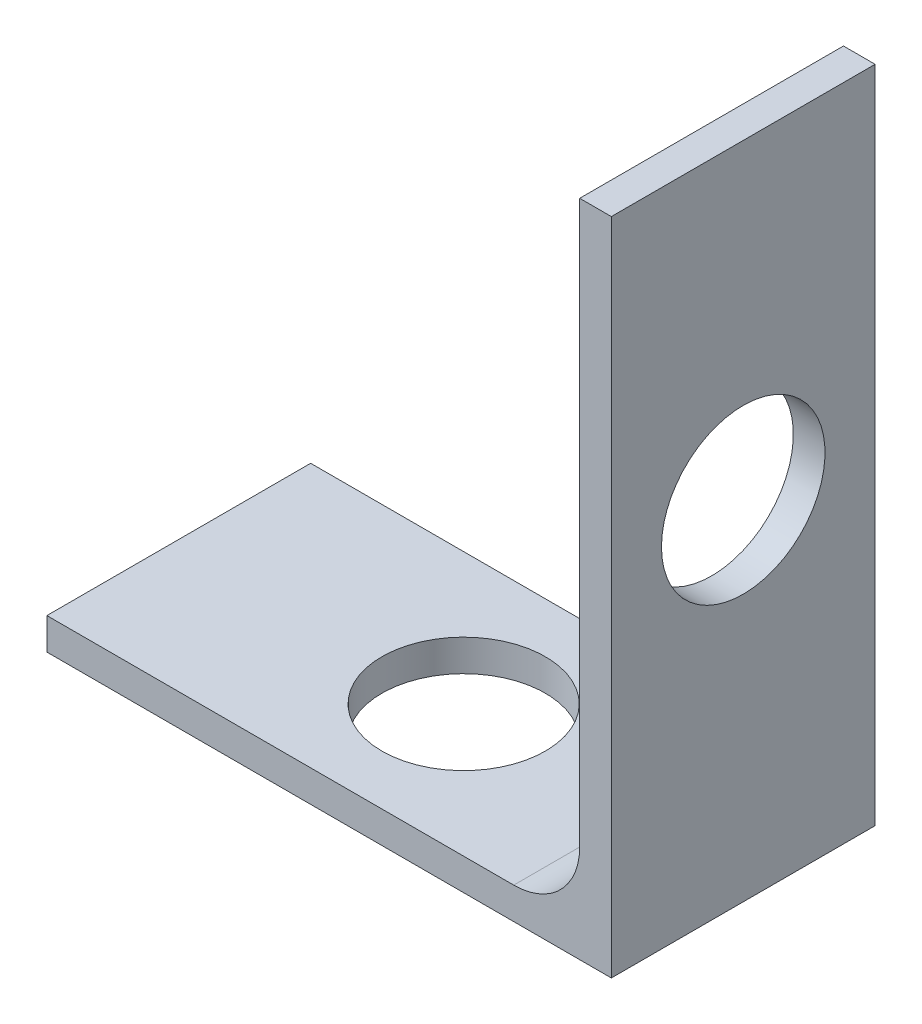
SolidWorks part; units mm, degrees
material "1060 Alloy"
ref_plane "Front Plane" through (0, 0, 0) normal (0, 0, 1) x (1, 0, 0)
ref_plane "Top Plane" through (0, 0, 0) normal (0, 1, 0) x (1, 0, 0)
ref_plane "Right Plane" through (0, 0, 0) normal (1, 0, 0) x (0, 0, -1)
sketch "Sketch1" plane through (0, 0, 0) normal (0, 0, 1) x (1, 0, 0)
  line L0 (0, 0) -> (27.178, 0)
  line L1 (27.178, 0) -> (27.178, 31.75)
  line L2 (0, 0) -> (0, 1.524)
  line L3 (0, 1.524) -> (25.654, 1.524)
  line L4 (25.654, 1.524) -> (25.654, 31.75)
  line L5 (25.654, 31.75) -> (27.178, 31.75)
  dimension "Height" = 31.75
  dimension "Depth" = 27.178
  dimension "Width2" = 1.524
  dimension "Width1" = 1.524
extrude "Boss-Extrude1" add sketch "Sketch1" along normal blind 12.7
sketch "Sketch2" plane through (25.654, 0, 0) normal (-1, 0, 0) x (0, 0, 1)
  line L8 (0, 31.75) -> (0, 1.524) construction
  line L9 (12.7, 0) -> (0, 0) construction
  circle A0 centre (6.35, 16.764) radius 3.937
  dimension "SideHoleDiameter" = 7.874
  dimension "SideHoleHorizontal" = 6.35
  dimension "SideHoleVertical" = 16.764
extrude "Cut-Extrude1" cut sketch "Sketch2" against normal blind 6.35
sketch "Sketch4" plane through (0, 1.524, 0) normal (0, 1, 0) x (1, 0, 0)
  line L0 (25.654, -12.7) -> (25.654, 0) construction
  line L6 (25.654, 0) -> (0, 0) construction
  circle A0 centre (13.716, -6.35) radius 3.937
  dimension "D1" = 7.874
  dimension "BottomHoleHorizontal" = 11.938
  dimension "BottomHoleVertical" = 6.35
extrude "Cut-Extrude2" cut sketch "Sketch4" against normal blind 6.35
fillet "Fillet2" radius 3.175 1 edges at (25.654, 1.524, 6.35) type face fillet first side face at (25.654, 16.764, 10.287) second side face at (13.716, 1.524, 10.287)
equation "\"height\"=1.25"
equation "\"width\"= .06in"
equation "\"depth\"= 1.07in"
equation "\"extrusion\"= .5in"
equation "\"side hole diameter\"= .31in"
equation "\"horizontal side hole\"= .25in"
equation "\"vertical side hole\"= .66in"
equation "\"bottom hole diameter\"= .31in"
equation "\"horizontal bottom hole\"= .47in"
equation "\"vertical bottom hole\"= .25in"
